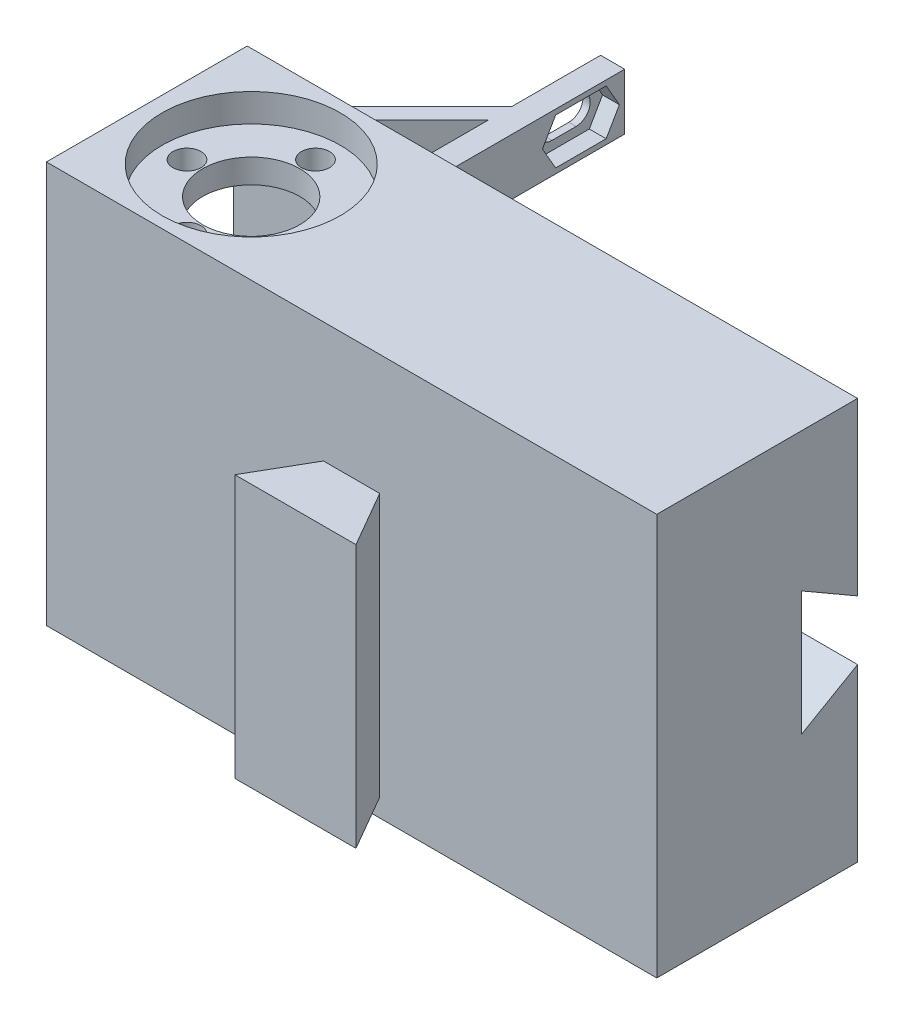
SolidWorks part; units mm, degrees
ref_plane "Front Plane" through (0, 0, 0) normal (0, 0, 1) x (1, 0, 0)
ref_plane "Top Plane" through (0, 0, 0) normal (0, 1, 0) x (1, 0, 0)
ref_plane "Right Plane" through (0, 0, 0) normal (1, 0, 0) x (0, 0, -1)
sketch "Sketch1" plane through (0, 0, 0) normal (0, 0, 1) x (1, 0, 0)
  line L0 (0, -25) -> (-38, -25)
  line L1 (-38, -25) -> (-38, 25)
  line L2 (-38, 25) -> (0, 25)
  line L3 (0, 25) -> (0, -25)
  point P7 (-38, 0)
  dimension "D1" = 50
  dimension "D2" = 38
extrude "Boss-Extrude1" add sketch "Sketch1" along normal blind 25
sketch "Sketch2" plane through (0, 0, 0) normal (0, 1, 0) x (0, 0, -1)
  line L1 (-25, 0) -> (-25, 38) construction
  line L2 (-25, 3.5) -> (-32, 7.5415)
  line L3 (-25, 0) -> (-25, 38)
  line L4 (-25, 0) -> (-32, 0)
  line L5 (-32, 0) -> (-32, 7.5415)
  dimension "D1" = 3.5
  dimension "D2" = 60
  dimension "D3" = 7
extrude "Boss-Extrude2" add sketch "Sketch2" against normal blind 22.75 and the other way blind 10 contours L2 region at (-2.8836, 0, 28.927)
sketch "Sketch3" plane through (0, 0, 0) normal (1, 0, 0) x (0, 0, -1)
  line L0 (0, 3.7) -> (-7, 7.7415)
  line L1 (0, -25) -> (0, 25) construction
  line L2 (-7, 7.7415) -> (-7, -7.7415)
  line L3 (-7, -7.7415) -> (0, -3.7)
  line L4 (0, -25) -> (0, 25)
  point P4 (-7, 0)
  line M4 (0, -25) -> (0, 25)
  dimension "D2" = 60
  dimension "D3" = 7
  dimension "D1" = 60
  dimension "D4" = 7.4
extrude "Cut-Extrude1" cut sketch "Sketch3" against normal blind 10 contours L2 L3 L0 M4 region at (0, 0, 3.9121)
mirror "Mirror1" about plane through (0, 0, 0) normal (1, 0, 0) of "Cut-Extrude1", "Boss-Extrude1", "Boss-Extrude2"
sketch "Sketch4" plane through (38, 0, 0) normal (1, 0, 0) x (0, 0, -1)
  line L0 (0, -3.7) -> (0, 3.7) construction
  line L1 (-7, -7.7415) -> (0, -3.7) construction
  line L2 (-7, 7.7415) -> (-7, -7.7415) construction
  line L3 (0, 3.7) -> (-7, 7.7415) construction
  line L4 (0, -3.7) -> (0, 3.7)
  line L5 (-7, -7.7415) -> (0, -3.7)
  line L6 (-7, 7.7415) -> (-7, -7.7415)
  line L7 (0, 3.7) -> (-7, 7.7415)
extrude "Cut-Extrude2" cut sketch "Sketch4" against normal up to next and the other way through all
sketch "Sketch14" plane through (-38, 0, 0) normal (-1, 0, 0) x (0, 0, 1)
  line L0 (25, 12.5) -> (25, -12.5)
  line L1 (25, 25) -> (25, -25) construction
  line L5 (22, 12.5) -> (22, -12.5)
  line L6 (25, 12.5) -> (22, 12.5)
  line L7 (25, -12.5) -> (22, -12.5)
  point P6 (25, 0)
  dimension "D1" = 25
  dimension "D2" = 3
extrude "Boss-Extrude4" [suppressed] add sketch "Sketch14" along normal blind 25
sketch "Sketch15" plane through (0, 25, 0) normal (0, 1, 0) x (1, 0, 0)
  line L0 (-38, -25) -> (-38, 0) construction
  line L1 (-38, -25) -> (-38, 0)
  line L2 (-10, 0) -> (38, 0) construction
  line L3 (-10, 0) -> (38, 0)
  circle A0 centre (-25, -12.5) radius 11.1
  point P9 (-38, -12.5)
  line M2 (38, 0) -> (-38, 0)
  dimension "D1" = 22.2
  dimension "D2" = 15
extrude "Cut-Extrude8" cut sketch "Sketch15" against normal blind 3.5 contours A0 M2 region at (-25, 25, 12.5)
ref_axis "Axis1" through (-25, 24.9785, 12.5) along (0, 1, 0)
sketch "Sketch16" plane through (0, 21.5, 0) normal (0, 1, 0) x (1, 0, 0)
  circle A0 centre (-25, -12.5) radius 6.05
  dimension "D1" = 12.1
extrude "Cut-Extrude9" cut sketch "Sketch16" against normal blind 19
sketch "Sketch17" plane through (0, 2.5, 0) normal (0, 1, 0) x (1, 0, 0)
  line L4 (-25, -5) -> (-38, -5)
  line L5 (-38, -25) -> (-38, 0) construction
  line L6 (-38, -5) -> (-38, -20)
  line L7 (-38, -20) -> (-25, -20)
  arc A2 (-25, -20) -> (-25, -5) centre (-25, -12.5) ccw
  circle M5 centre (-25, -12.5) radius 6.05
  dimension "D1" = 15
extrude "Cut-Extrude10" cut sketch "Sketch17" against normal blind 5.8 contours L4 L6 L7 | M5 region at (-17.754, 2.5, 12.5) region at (-25, 2.5, 12.5)
sketch "Sketch18" plane through (0, 2.5, 0) normal (0, -1, 0) x (1, 0, 0)
  line L4 (-25, 18.55) -> (-38, 18.55)
  line L5 (-38, 5) -> (-38, 20) construction
  line L6 (-38, 18.55) -> (-38, 6.45)
  line L7 (-38, 6.45) -> (-25, 6.45)
  circle A2 centre (-25, 12.5) radius 6.05 construction
  arc A3 (-25, 6.45) -> (-25, 18.55) centre (-25, 12.5) ccw
extrude "Cut-Extrude11" cut sketch "Sketch18" against normal blind 16
sketch "Sketch19" plane through (0, 21.5, 0) normal (0, 1, 0) x (1, 0, 0)
  circle A0 centre (-25, -12.5) radius 8 construction
  circle A1 centre (-33, -12.5) radius 1.75
  dimension "D1" = 16
  dimension "D2" = 3.5
extrude "Cut-Extrude12" cut sketch "Sketch19" against normal blind 19
pattern_circular "CirPattern1" count 2 every 90 about axis through (-25, 24.9785, 12.5) along (0, 1, 0) of "Cut-Extrude12" other way count 2
sketch "Sketch20" plane through (0, -3.3, 0) normal (0, 1, 0) x (1, 0, 0)
  circle A0 centre (-25, -12.5) radius 4.15
  dimension "D1" = 8.3
extrude "Cut-Extrude13" cut sketch "Sketch20" against normal through all
sketch "Sketch21" plane through (0, 18.5, 0) normal (0, -1, 0) x (1, 0, 0)
  line L0 (-38, 1.7) -> (-38, 23.3)
  line L1 (-38, 23.3) -> (-22.2, 23.3)
  line L2 (-22.2, 23.3) -> (-22.2, 1.7)
  line L3 (-22.2, 1.7) -> (-38, 1.7)
  line L4 (-38, 25) -> (-38, 0) construction
  line L5 (-38, 25) -> (-38, 0)
  circle A4 centre (-25, 20.5) radius 1.75 construction
  circle A5 centre (-25, 4.5) radius 1.75 construction
  circle A6 centre (-25, 20.5) radius 1.75
  circle A7 centre (-25, 4.5) radius 1.75
  point P2 (-22.2, 12.5)
  dimension "D1" = 2.8
  dimension "D2" = 2.8
extrude "Cut-Extrude14" cut sketch "Sketch21" along normal blind 16 contours L3 L2 L1 L0 region at (-30.4047, 18.5, 12.5)
sketch "Sketch22" plane through (0, 0, 0) normal (0, 0, -1) x (-1, 0, 0)
  line L4 (16, 21) -> (19, 21)
  line L5 (19, 21) -> (19, 14)
  line L6 (19, 14) -> (16, 14)
  line L7 (16, 14) -> (16, 21)
  line L8 (16, -14) -> (19, -14)
  line L9 (19, -14) -> (19, -21)
  line L10 (19, -21) -> (16, -21)
  line L11 (16, -21) -> (16, -14)
  line L16 (16, 14) -> (16, -14) construction
  line L18 (38, 25) -> (38, -25) construction
  point P0 (16, 0)
  point P1 (16, 17.5)
  point P2 (16, -17.5)
  dimension "D1" = 7
  dimension "D2" = 35
  dimension "D3" = 3
  dimension "D6" = 22
extrude "Boss-Extrude5" add sketch "Sketch22" along normal blind 25
sketch "Sketch23" plane through (-19, 0, 0) normal (-1, 0, 0) x (0, 0, 1)
  line L0 (-25, 14) -> (-25, 21) construction
  line L1 (-25, 14) -> (-25, 21)
  line L2 (-25, -21) -> (-25, -14) construction
  line L3 (-25, -21) -> (-25, -14)
  line L4 (0, 25) -> (0, -25) construction
  line L5 (-21.05, 17.5) -> (-18.05, 17.5) construction
  line L6 (-21.05, 19.25) -> (-18.05, 19.25)
  line L7 (-21.05, 15.75) -> (-18.05, 15.75)
  line L8 (-21.05, -17.5) -> (-18.05, -17.5) construction
  line L9 (-21.05, -15.75) -> (-18.05, -15.75)
  line L10 (-21.05, -19.25) -> (-18.05, -19.25)
  circle A0 centre (-21.05, 17.5) radius 1.75
  circle A1 centre (-21.05, -17.5) radius 1.75
  arc A2 (-21.05, 19.25) -> (-21.05, 15.75) centre (-21.05, 17.5) ccw
  arc A3 (-18.05, 15.75) -> (-18.05, 19.25) centre (-18.05, 17.5) ccw
  arc A4 (-21.05, -15.75) -> (-21.05, -19.25) centre (-21.05, -17.5) ccw
  arc A5 (-18.05, -19.25) -> (-18.05, -15.75) centre (-18.05, -17.5) ccw
  point P9 (-25, 17.5)
  point P10 (-19.55, 17.5)
  point P11 (-25, -17.5)
  point P18 (-19.55, -17.5)
  dimension "D1" = 3.5
  dimension "D2" = 21.05
  dimension "D3" = 3
extrude "Cut-Extrude15" cut sketch "Sketch23" against normal blind 10 contours A0 | L7 A3 L6 A0 | A1 | L10 A5 L9 A1 region at (-19, 17.5, -18.1756) region at (-19, 17.5, -21.05) region at (-19, -17.5, -18.1756) region at (-19, -17.5, -21.05)
sketch "Sketch24" plane through (-16, 0, 0) normal (-1, 0, 0) x (0, 0, 1)
  line L1 (-17.7591, 17.5) -> (-19.4046, 20.35)
  line L2 (-19.4046, 20.35) -> (-22.6954, 20.35)
  line L3 (-22.6954, 20.35) -> (-24.3409, 17.5)
  line L4 (-24.3409, 17.5) -> (-22.6954, 14.65)
  line L5 (-22.6954, 14.65) -> (-19.4046, 14.65)
  line L6 (-19.4046, 14.65) -> (-17.7591, 17.5)
  line L7 (-17.7591, -17.5) -> (-19.4046, -14.65)
  line L8 (-19.4046, -14.65) -> (-22.6954, -14.65)
  line L9 (-22.6954, -14.65) -> (-24.3409, -17.5)
  line L10 (-24.3409, -17.5) -> (-22.6954, -20.35)
  line L11 (-22.6954, -20.35) -> (-19.4046, -20.35)
  line L12 (-19.4046, -20.35) -> (-17.7591, -17.5)
  line L13 (-14.7591, -17.5) -> (-16.4046, -14.65)
  line L14 (-16.4046, -14.65) -> (-19.6954, -14.65)
  line L15 (-19.6954, -14.65) -> (-21.3409, -17.5)
  line L16 (-21.3409, -17.5) -> (-19.6954, -20.35)
  line L17 (-19.6954, -20.35) -> (-16.4046, -20.35)
  line L18 (-16.4046, -20.35) -> (-14.7591, -17.5)
  line L19 (-14.7591, 17.5) -> (-16.4046, 20.35)
  line L20 (-16.4046, 20.35) -> (-19.6954, 20.35)
  line L21 (-19.6954, 20.35) -> (-21.3409, 17.5)
  line L22 (-21.3409, 17.5) -> (-19.6954, 14.65)
  line L23 (-19.6954, 14.65) -> (-16.4046, 14.65)
  line L24 (-16.4046, 14.65) -> (-14.7591, 17.5)
  circle A0 centre (-21.05, 17.5) radius 2.85 construction
  circle A1 centre (-21.05, -17.5) radius 2.85 construction
  arc A2 (-18.05, -19.25) -> (-18.05, -15.75) centre (-18.05, -17.5) ccw construction
  arc A3 (-18.05, -19.25) -> (-18.05, -15.75) centre (-18.05, -17.5) ccw
  circle A4 centre (-18.05, -17.5) radius 2.85 construction
  circle A5 centre (-18.05, 17.5) radius 2.85 construction
  arc M18 (-21.05, 19.25) -> (-21.05, 15.75) centre (-21.05, 17.5) ccw
  line M23 (-18.05, 19.25) -> (-21.05, 19.25)
  line M24 (-21.05, 15.75) -> (-18.05, 15.75)
  arc M25 (-18.05, 15.75) -> (-18.05, 19.25) centre (-18.05, 17.5) ccw
  dimension "D1" = 5.7
extrude "Cut-Extrude16" cut sketch "Sketch24" along normal blind 2.1 contours L22 L5 L4 L3 L2 L21 M24 M23 M18 | L24 L23 L6 L1 L20 L19 M24 M25 M23 | L21 L2 L1 M23 | L22 L6 L5 M24 | L16 L15 L8 L7 L12 L11 | L15 L16 L11 L10 L9 L8 | L18 L17 L12 L7 L14 L13 region at (-16, 19.6743, -19.55) region at (-16, 19.8368, -19.0233) region at (-16, 15.3257, -19.55) region at (-16, 19.3235, -20.6903) region at (-16, -17.5, -19.55) region at (-16, -17.5, -17.0818) region at (-16, -17.5, -22.0182)
sketch "Sketch25" plane through (-38, 0, 0) normal (-1, 0, 0) x (0, 0, 1)
  line L0 (0, 0) -> (-6.55, 0)
  line L1 (0, 25) -> (0, -25) construction
  line L2 (-14.55, 12.6491) -> (0, 12.6491)
  line L3 (0, 12.6491) -> (0, -12.6491)
  line L4 (0, -12.6491) -> (-14.55, -12.6491)
  arc A0 (-14.55, 12.6491) -> (-14.55, -12.6491) centre (-20.55, 0) cw
  line M18 (0, 25) -> (0, -25)
  dimension "D2" = 14
  dimension "D1" = 6.55
  dimension "D3" = 8
extrude "Boss-Extrude6" [suppressed] add sketch "Sketch25" against normal blind 12.1 contours L0 A0 L4 M18 | L2 A0 L0 M18
sketch "Sketch26" plane through (0, -21, 0) normal (0, -1, 0) x (1, 0, 0)
  line L0 (-19, -14) -> (-33, 0)
  line L1 (-19, -25) -> (-19, 0) construction
  line L2 (-38, 0) -> (38, 0) construction
  line L3 (-33, 0) -> (-30, 0)
  line L4 (-30, 0) -> (-19, -11)
  line L5 (-19, -11) -> (-19, -14)
  dimension "D1" = 11
  dimension "D2" = 45
  dimension "D3" = 3
extrude "Boss-Extrude7" add sketch "Sketch26" against normal up to surface (7 mm away) up to face at (-17.5, -14, -12.5)
sketch "Sketch28" plane through (0, 21, 0) normal (0, 1, 0) x (1, 0, 0)
  line L0 (-33, 0) -> (-30, 0) construction
  line L1 (-30, 0) -> (-19, 11) construction
  line L2 (-19, 14) -> (-33, 0) construction
  line L3 (-33, 0) -> (-30, 0)
  line L4 (-30, 0) -> (-19, 11)
  line L5 (-19, 14) -> (-33, 0)
  line L6 (-19, 14) -> (-19, 11)
extrude "Boss-Extrude8" add sketch "Sketch28" against normal up to surface (7 mm away) up to face at (-17.5, 14, -12.5)
equation "\"Width\"= 76mm"
equation "\"Height\"= 50mm"
equation "\"SpringD\"= 5"
equation "\"D1@Sketch1\"=\"Height\""
equation "\"D2@Sketch1\"=\"Width\"/2"
equation "\"DovetailAngle\" = 60deg"
equation "\"DovetailHeight\" = 7mm"
equation "\"DovetailBase\" = 7mm"
equation "\"D4@Sketch2\"=\"DovetailHeight\""
equation "\"D1@Boss-Extrude2\"=16.75+6"
equation "\"D3@Sketch3\"=\"DovetailHeight\""
equation "\"D4@Sketch3\"=\"DovetailBase\" + 0.4"
equation "\"D1@Cut-Extrude1\"=\"Width\"/2-28"
equation "\"D1@Sketch2\"=\"DovetailBase\"/2"
equation "\"D2@Sketch2\"=\"DovetailAngle\""
equation "\"D3@Sketch2\"=\"DovetailHeight\""
